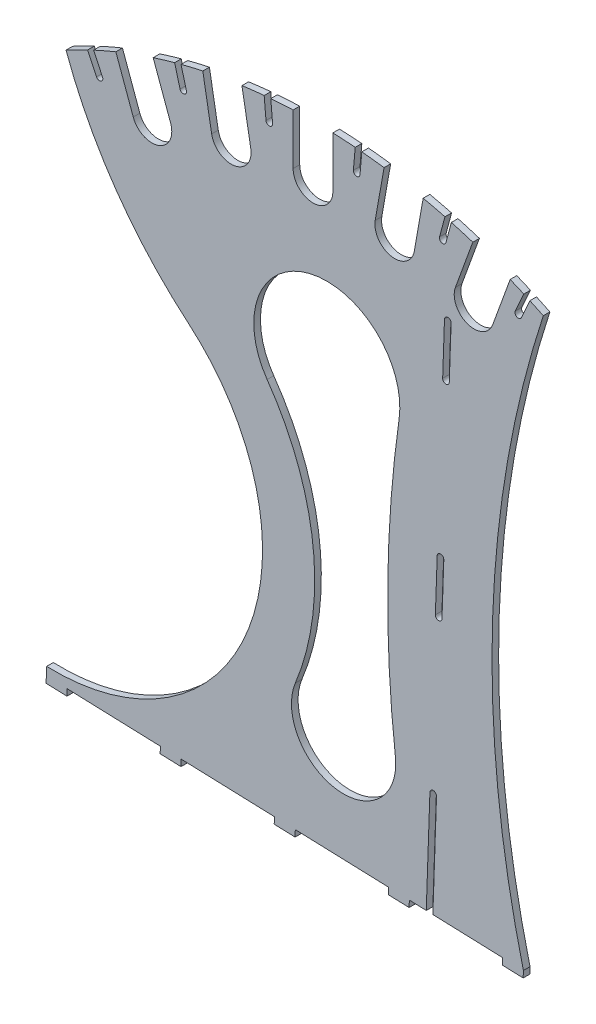
SolidWorks part; units mm, degrees
ref_plane "Front Plane" through (0, 0, 0) normal (0, 0, 1) x (1, 0, 0)
ref_plane "Top Plane" through (0, 0, 0) normal (0, 1, 0) x (1, 0, 0)
ref_plane "Right Plane" through (0, 0, 0) normal (1, 0, 0) x (0, 0, -1)
sketch "Sketch1" plane through (0, 0, 0) normal (0, 0, 1) x (1, 0, 0)
  line L0 (124.6306, 74.9072) -> (-116.031, 83.3183) construction
  line L1 (124.6306, 74.9072) -> (-116.031, 83.3183)
  line L2 (-110.0347, 83.1087) -> (-100.7754, 348.038)
  line L3 (-62.3445, 364.6831) -> (-73.6208, 360.5788) construction
  line L4 (128.3168, 352.1551) -> (118.6343, 75.1167)
  line L5 (-19.854, 374.9856) -> (-31.6717, 372.9018) construction
  line L6 (-67.9827, 362.631) -> (-59.4322, 339.1386) construction
  line L7 (17.78, 377.825) -> (17.78, 127) construction
  line L8 (-59.0321, 365.8887) -> (-50.4816, 342.3964)
  line L9 (-76.9332, 359.3732) -> (-68.3827, 335.8809)
  line L10 (17.78, 127) -> (-59.4322, 339.1386) construction
  line L11 (-25.7628, 373.9437) -> (-21.4216, 349.3235) construction
  line L12 (-16.3825, 375.5977) -> (-12.0413, 350.9775)
  line L13 (-35.1431, 372.2897) -> (-30.8019, 347.6695)
  line L14 (17.78, 377.825) -> (17.78, 352.825) construction
  line L15 (27.305, 377.825) -> (27.305, 352.825)
  line L16 (8.255, 377.825) -> (8.255, 352.825)
  line L17 (103.5427, 362.631) -> (94.9922, 339.1386) construction
  line L18 (94.5921, 365.8887) -> (86.0416, 342.3964)
  line L19 (112.4932, 359.3732) -> (103.9427, 335.8809)
  line L20 (61.3228, 373.9437) -> (56.9816, 349.3235) construction
  line L21 (51.9425, 375.5977) -> (47.6013, 350.9775)
  line L22 (70.7031, 372.2897) -> (66.3619, 347.6695)
  line L23 (-110.0347, 83.1087) -> (-110.1456, 79.9357)
  line L24 (-110.1456, 79.9357) -> (-100.1517, 79.5864)
  line L25 (-100.1517, 79.5864) -> (-100.0408, 82.7594)
  line L26 (-116.1419, 80.1452) -> (124.5197, 71.7341) construction
  line L27 (118.6343, 75.1167) -> (118.5234, 71.9437)
  line L28 (118.5234, 71.9437) -> (108.5295, 72.293)
  line L29 (108.5295, 72.293) -> (108.6404, 75.466)
  line L30 (-55.3659, 81.1981) -> (-55.4768, 78.025)
  line L31 (-55.4768, 78.025) -> (-45.4829, 77.6757)
  line L32 (-45.4829, 77.6757) -> (-45.372, 80.8488)
  line L33 (-0.6971, 79.2874) -> (-0.808, 76.1143)
  line L34 (-0.808, 76.1143) -> (9.1859, 75.765)
  line L35 (9.1859, 75.765) -> (9.2968, 78.9381)
  line L36 (53.9716, 77.3767) -> (53.8607, 74.2036)
  line L37 (53.8607, 74.2036) -> (63.8546, 73.8544)
  line L38 (63.8546, 73.8544) -> (63.9655, 77.0274)
  line L39 (4.2998, 79.1127) -> (4.1889, 75.9397) construction
  line L40 (-100.1517, 79.5864) -> (-0.808, 76.1143) construction
  line L41 (9.1859, 75.765) -> (108.5295, 72.293) construction
  line L42 (73.6618, 76.6885) -> (75.4082, 126.658) construction
  line L43 (72.0752, 76.744) -> (73.8217, 126.7135)
  line L44 (75.2483, 76.6331) -> (76.9947, 126.6026)
  line L45 (78.0278, 201.6123) -> (78.9011, 226.597) construction
  line L46 (76.4413, 201.6677) -> (77.3145, 226.6525)
  line L47 (79.6144, 201.5568) -> (80.4876, 226.5416)
  line L48 (81.5207, 301.5512) -> (82.3939, 326.536) construction
  line L49 (79.9342, 301.6067) -> (80.8074, 326.5914)
  line L50 (83.1072, 301.4958) -> (83.9805, 326.4805)
  arc A0 (128.3168, 352.1551) -> (-100.7754, 348.038) centre (17.78, 127) ccw
  arc A1 (11.78, 377.7532) -> (-19.854, 374.9856) centre (17.78, 127) ccw construction
  arc A2 (-112.7928, 341.1587) -> (-138.8048, 322.9448) centre (17.78, 127) ccw construction
  arc A3 (128.2976, 351.6073) -> (-100.7956, 347.4596) centre (17.78, 127) ccw
  arc A4 (128.0964, 351.7062) -> (-100.5391, 347.5974) centre (17.78, 127) ccw construction
  arc A5 (-59.0321, 365.8887) -> (-76.9332, 359.3732) centre (-67.9827, 362.631) ccw
  arc A6 (-68.3827, 335.8809) -> (-50.4816, 342.3964) centre (-59.4322, 339.1386) ccw
  arc A7 (-16.3825, 375.5977) -> (-35.1431, 372.2897) centre (-25.7628, 373.9437) ccw
  arc A8 (-30.8019, 347.6695) -> (-12.0413, 350.9775) centre (-21.4216, 349.3235) ccw
  arc A9 (27.305, 377.825) -> (8.255, 377.825) centre (17.78, 377.825) ccw
  arc A10 (8.255, 352.825) -> (27.305, 352.825) centre (17.78, 352.825) ccw
  arc A11 (-100.7754, 348.038) -> (-41.8463, 263.4189) centre (87.265, 416.1614) ccw
  arc A12 (-109.8949, 87.1087) -> (-41.8463, 263.4189) centre (-106.402, 187.0477) ccw
  arc A13 (128.3168, 352.1551) -> (118.6343, 75.1167) centre (603.5874, 196.856) ccw
  arc A14 (94.5921, 365.8887) -> (112.4932, 359.3732) centre (103.5427, 362.631) cw
  arc A15 (103.9427, 335.8809) -> (86.0416, 342.3964) centre (94.9922, 339.1386) cw
  arc A16 (51.9425, 375.5977) -> (70.7031, 372.2897) centre (61.3228, 373.9437) cw
  arc A17 (66.3619, 347.6695) -> (47.6013, 350.9775) centre (56.9816, 349.3235) cw
  arc A18 (72.0752, 76.744) -> (75.2483, 76.6331) centre (73.6618, 76.6885) ccw
  arc A19 (76.9947, 126.6026) -> (73.8217, 126.7135) centre (75.4082, 126.658) ccw
  arc A20 (76.4413, 201.6677) -> (79.6144, 201.5568) centre (78.0278, 201.6123) ccw
  arc A21 (80.4876, 226.5416) -> (77.3145, 226.6525) centre (78.9011, 226.597) ccw
  arc A22 (79.9342, 301.6067) -> (83.1072, 301.4958) centre (81.5207, 301.5512) ccw
  arc A23 (83.9805, 326.4805) -> (80.8074, 326.5914) centre (82.3939, 326.536) ccw
  point P3 (-25.7628, 373.9437)
  point P5 (-67.9827, 362.631)
  point P28 (-63.7074, 350.8848)
  point P35 (-23.5922, 361.6336)
  point P41 (17.78, 365.325)
  point P55 (99.2674, 350.8848)
  point P62 (59.1522, 361.6336)
  point P83 (4.2998, 79.1127)
  point P88 (4.1889, 75.9397)
  point P89 (-50.4799, 77.8503)
  point P90 (58.8577, 74.029)
  point P91 (74.535, 101.6733)
  point P98 (78.4644, 214.1046)
  point P107 (81.9573, 314.0436)
  dimension "D8" = 200
  dimension "D9" = 100
  dimension "D11" = 1000
  dimension "D19" = 250.325
  dimension "D1" = 6
  dimension "D2" = 6
  dimension "D4" = 20
  dimension "D5" = 19.05
  dimension "D6" = 25
  dimension "D7" = 10
  dimension "D10" = 4
  dimension "D12" = 10
  dimension "D13" = 3.175
  dimension "D14" = 50
  dimension "D15" = 45
  dimension "D16" = 25
  dimension "D17" = 100
  dimension "D18" = 100
  dimension "D3" = 0.5
extrude "Boss-Extrude1" add sketch "Sketch1" along normal mid plane 3.175 contours L4 L2 L1 | L24 L25 L1 L23 | L29 L28 L27 L1 | L37 L38 L1 L36 | L34 L35 L1 L33 | L31 L32 L1 L30 region at (113.5819, 73.7049, 0) region at (30.2021, 227.5758, 0) region at (58.9131, 75.6155, 0) region at (4.2444, 77.5262, 0) region at (-50.4244, 79.4369, 0) region at (-105.0932, 81.3476, 0)
ref_plane "Plane1" through (80, 0, 0) normal (-1, 0, 0) x (0, 0, 1)
ref_plane "Plane2" through (115.8674, -4.0496, 0) normal (0.9994, -0.0349, 0) x (0, 0, -1)
ref_plane "Plane3" through (65.8979, -2.3031, 0) normal (0.9994, -0.0349, 0) x (0, 0, -1)
sketch "Sketch2" plane through (0, 0, 1.5875) normal (0, 0, 1) x (1, 0, 0)
  arc A0 (59.0607, 274.2552) -> (-4.2059, 259.0266) centre (24.409, 279.1806) ccw
  arc A1 (-109.8949, 87.1087) -> (-41.8463, 263.4189) centre (-106.402, 187.0477) ccw construction
  arc A2 (9.3094, 139.7627) -> (57.2837, 133.1992) centre (32.4517, 130.3057) ccw
  arc A3 (9.3094, 139.7627) -> (-4.2059, 259.0266) centre (-106.402, 187.0477) ccw
  arc A5 (59.0607, 274.2552) -> (57.2837, 133.1992) centre (603.5874, 196.856) ccw
  arc A6 (128.1602, 351.6749) -> (118.6343, 75.1167) centre (603.5874, 196.856) ccw construction
  dimension "D1" = 70
  dimension "D2" = 25
  dimension "D3" = 25
  dimension "D4" = 50
extrude "Cut-Extrude1" cut sketch "Sketch2" against normal blind 10
sketch "Sketch3" plane through (0, 0, 1.5875) normal (0, 0, 1) x (1, 0, 0)
  line L0 (-88.8119, 353.4967) -> (-84.5538, 344.4486) construction
  line L1 (-87.3755, 354.1727) -> (-83.1174, 345.1246)
  line L2 (-90.2483, 352.8207) -> (-85.9902, 343.7726)
  line L3 (-47.0089, 368.7954) -> (-44.4207, 359.1361) construction
  line L4 (-45.4755, 369.2063) -> (-42.8873, 359.547)
  line L5 (-48.5423, 368.3845) -> (-45.9541, 358.7252)
  line L6 (-4.0373, 376.3724) -> (-3.1657, 366.4105) construction
  line L7 (-2.4558, 376.5108) -> (-1.5842, 366.5489)
  line L8 (-5.6187, 376.2341) -> (-4.7472, 366.2721)
  line L9 (39.5973, 376.3724) -> (38.7257, 366.4105) construction
  line L10 (41.1787, 376.2341) -> (40.3072, 366.2721)
  line L11 (38.0158, 376.5108) -> (37.1442, 366.5489)
  line L12 (82.5689, 368.7954) -> (79.9807, 359.1361) construction
  line L13 (84.1023, 368.3845) -> (81.5141, 358.7252)
  line L14 (81.0355, 369.2063) -> (78.4473, 359.547)
  line L15 (120.2844, 355.3757) -> (116.1896, 346.2525) construction
  line L16 (121.7327, 354.7256) -> (117.6379, 345.6025)
  line L17 (118.8361, 356.0257) -> (114.7412, 346.9026)
  arc A0 (-76.7248, 358.8005) -> (-100.6027, 347.5632) centre (17.78, 127) ccw construction
  arc A1 (-87.3755, 354.1727) -> (-90.2483, 352.8207) centre (-88.8119, 353.4967) ccw
  arc A2 (-85.9902, 343.7726) -> (-83.1174, 345.1246) centre (-84.5538, 344.4486) ccw
  arc A3 (-35.0373, 371.6895) -> (-58.8236, 365.3159) centre (17.78, 127) ccw construction
  arc A4 (-45.4755, 369.2063) -> (-48.5423, 368.3845) centre (-47.0089, 368.7954) ccw
  arc A5 (-45.9541, 358.7252) -> (-42.8873, 359.547) centre (-44.4207, 359.1361) ccw
  arc A6 (8.255, 377.1437) -> (-16.2767, 374.9975) centre (17.78, 127) ccw construction
  arc A7 (-2.4558, 376.5108) -> (-5.6187, 376.2341) centre (-4.0373, 376.3724) ccw
  arc A8 (-4.7472, 366.2721) -> (-1.5842, 366.5489) centre (-3.1657, 366.4105) ccw
  arc A9 (51.8367, 374.9975) -> (27.305, 377.1437) centre (17.78, 127) ccw construction
  arc A10 (41.1787, 376.2341) -> (38.0158, 376.5108) centre (39.5973, 376.3724) ccw
  arc A11 (37.1442, 366.5489) -> (40.3072, 366.2721) centre (38.7257, 366.4105) ccw
  arc A12 (94.3836, 365.3159) -> (70.5973, 371.6895) centre (17.78, 127) ccw construction
  arc A13 (84.1023, 368.3845) -> (81.0355, 369.2063) centre (82.5689, 368.7954) ccw
  arc A14 (78.4473, 359.547) -> (81.5141, 358.7252) centre (79.9807, 359.1361) ccw
  arc A15 (128.1602, 351.6749) -> (112.2848, 358.8005) centre (17.78, 127) ccw construction
  arc A16 (121.7327, 354.7256) -> (118.8361, 356.0257) centre (120.2844, 355.3757) ccw
  arc A17 (114.7412, 346.9026) -> (117.6379, 345.6025) centre (116.1896, 346.2525) ccw
  point P5 (-86.6829, 348.9727)
  point P10 (-45.7148, 363.9658)
  point P20 (-3.6015, 371.3915)
  point P30 (39.1615, 371.3915)
  point P40 (81.2748, 363.9658)
  point P50 (118.237, 350.8141)
  point P60 (0, 0)
  point P61 (17.78, 127)
  point P62 (0, 0)
  dimension "D1" = 3.175
  dimension "D2" = 10
extrude "Cut-Extrude2" cut sketch "Sketch3" against normal through all
